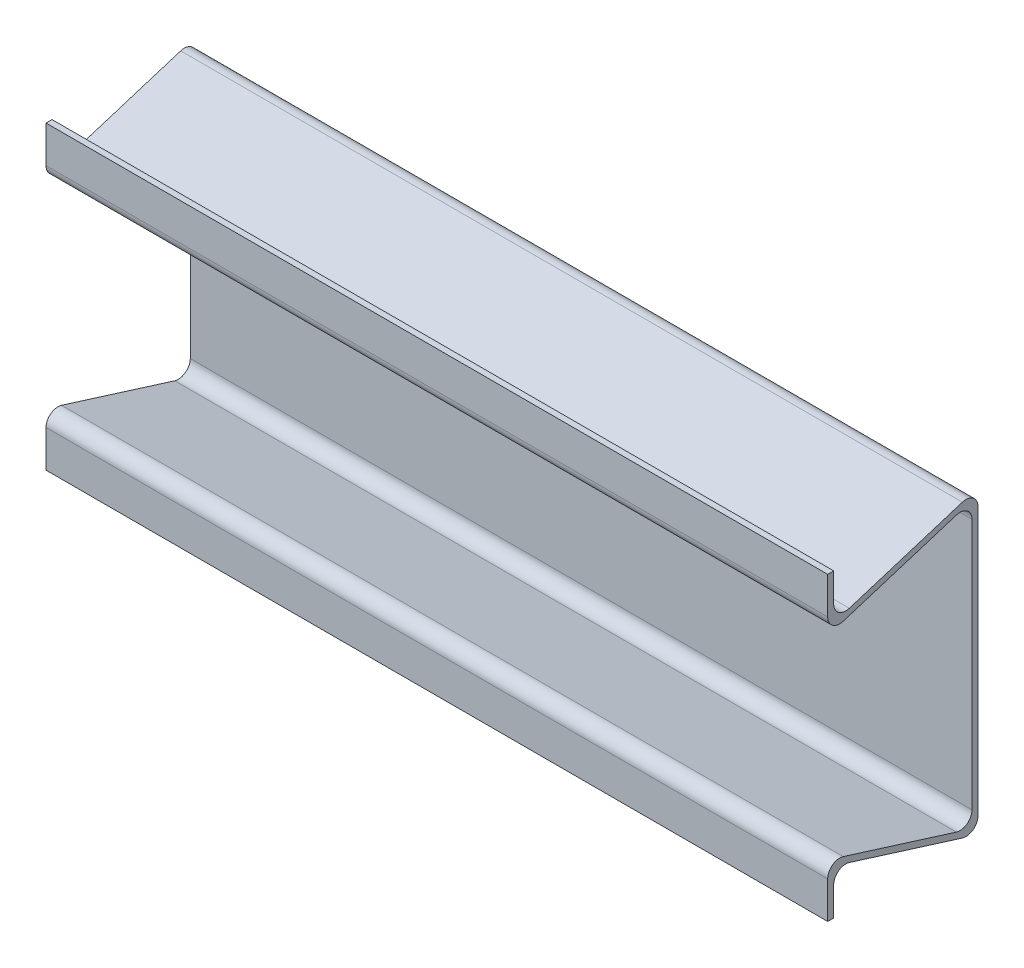
SolidWorks part; units mm, degrees
material "AISI 1020 Acero laminado en frío"
ref_plane "Alzado" through (0, 0, 0) normal (0, 0, 1) x (1, 0, 0)
ref_plane "Planta" through (0, 0, 0) normal (0, 1, 0) x (1, 0, 0)
ref_plane "Vista lateral" through (0, 0, 0) normal (1, 0, 0) x (0, 0, -1)
sketch "Croquis1" plane through (0, 0, 0) normal (1, 0, 0) x (0, 0, -1)
  line L0 (50, 50) -> (50, -50) construction
  line L1 (50, -50) -> (-50, -50) construction
  line L2 (-50, -50) -> (-50, 50) construction
  line L3 (-50, 50) -> (50, 50) construction
  line L4 (50, 50) -> (2, 35)
  line L5 (2, 35) -> (2, 50)
  line L6 (50, 50) -> (50, 0)
  line L7 (0, 0) -> (50, 0) construction
  line L8 (48, 47.2796) -> (48, 0)
  line L9 (48, 47.2796) -> (0, 32.2796)
  line L10 (0, 32.2796) -> (0, 50)
  line L11 (0, 50) -> (2, 50)
  line L12 (50, -50) -> (50, 0)
  line L13 (48, -47.2796) -> (48, 0)
  line L14 (48, -47.2796) -> (0, -32.2796)
  line L15 (50, -50) -> (2, -35)
  line L16 (0, -32.2796) -> (0, -50)
  line L17 (2, -35) -> (2, -50)
  line L18 (0, -50) -> (2, -50)
  point P3 (-50, 0)
  point P6 (0, 50)
  dimension "D1" = 100
  dimension "D2" = 2
  dimension "D3" = 15
extrude "Saliente-Extruir1" add sketch "Croquis1" along normal blind 130 and the other way blind 130
fillet "Redondeo1" radius 4 8 edges at (0, -35, -2) (0, -32.2796, 0) (0, -47.2796, -48) (0, -50, -50) (0, 50, -50) (0, 47.2796, -48) (0, 35, -2) (0, 32.2796, 0)
